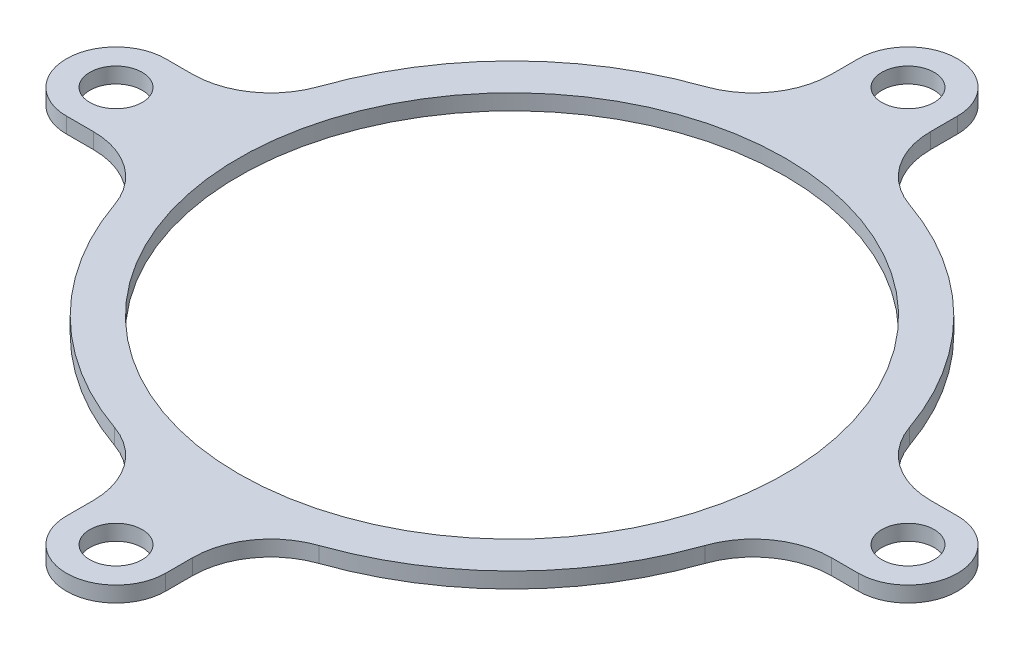
SolidWorks part; units mm, degrees
material "3003 Alloy"
ref_plane "Front Plane" through (0, 0, 0) normal (0, 0, 1) x (1, 0, 0)
ref_plane "Top Plane" through (0, 0, 0) normal (0, 1, 0) x (1, 0, 0)
ref_plane "Right Plane" through (0, 0, 0) normal (1, 0, 0) x (0, 0, -1)
sketch "Sketch1" plane through (0, 0, 0) normal (0, 1, 0) x (1, 0, 0)
  circle A0 centre (0, 0) radius 35
  circle A1 centre (0, 0) radius 40
  dimension "innerDiam" = 70
  dimension "outerDiam" = 80
extrude "Boss-Extrude1" add sketch "Sketch1" along normal mid plane 2
sketch "Sketch2" plane through (0, 1, 0) normal (0, 1, 0) x (1, 0, 0)
  line L0 (0, 0) -> (0, 38.8704) construction
  line L1 (-6.35, 47.2512) -> (-6.35, 50.7)
  line L2 (6.35, 50.7) -> (6.35, 47.2512)
  arc A0 (-6.35, 50.7) -> (6.35, 50.7) centre (0, 50.7) cw
  arc A1 (6.35, 47.2512) -> (13.08, 37.801) centre (16.35, 47.2512) ccw
  circle A2 centre (0, 0) radius 40 construction
  arc A3 (-6.35, 47.2512) -> (-13.08, 37.801) centre (-16.35, 47.2512) cw
  arc A4 (13.08, 37.801) -> (-13.08, 37.801) centre (0, 0) ccw
  circle A5 centre (0, 0) radius 50.7 construction
  circle A6 centre (0, 50.7) radius 3.35
  dimension "supportsDiam" = 101.4
  dimension "rodDiam" = 6.7
  dimension "D3" = 3
  dimension "D4" = 10
extrude "Boss-Extrude2" add sketch "Sketch2" against normal up to surface (2 mm away) up to face at (0, -1, 40)
pattern_circular "CirPattern1" count 4 over 360 about axis through (0, 1, 0) along (0, -1, 0) of "Boss-Extrude2" reverse direction yes
